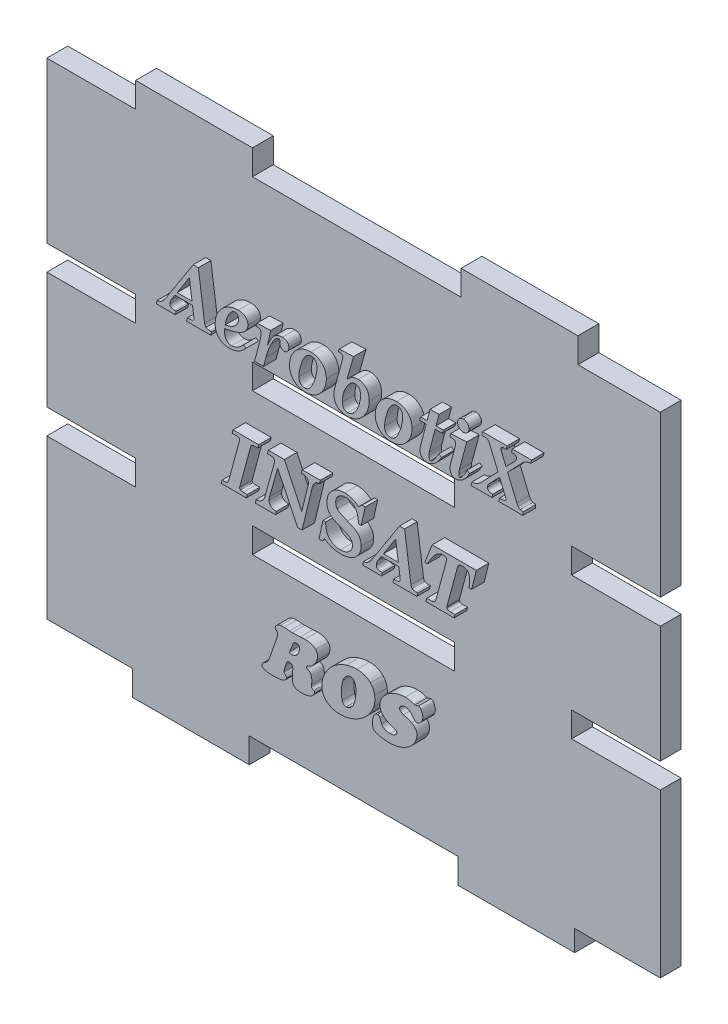
SolidWorks part; units mm, degrees
ref_plane "Front Plane" through (0, 0, 0) normal (0, 0, 1) x (1, 0, 0)
ref_plane "Top Plane" through (0, 0, 0) normal (0, 1, 0) x (1, 0, 0)
ref_plane "Right Plane" through (0, 0, 0) normal (1, 0, 0) x (0, 0, -1)
sketch "Sketch1" plane through (0, 0, 0) normal (0, 0, 1) x (1, 0, 0)
  line L5 (-24, -72.5496) -> (-73.5, -72.5496)
  line L6 (-73.5, 72.5496) -> (73.5, 72.5496)
  line L9 (-73.5, 72.5496) -> (-73.5, -72.5496)
  line L24 (73.5, 72.5496) -> (73.5, -72.5496)
  line L25 (-73.5, 72.5496) -> (73.5, -72.5496) construction
  line L26 (-73.5, -72.5496) -> (73.5, 72.5496) construction
  line L28 (-24, -72.5496) -> (-24, -67.5496)
  line L29 (-24, -67.5496) -> (24, -67.5496)
  line L30 (24, -72.5496) -> (24, -67.5496)
  line L31 (24, -72.5496) -> (73.5, -72.5496)
  line L32 (73.5, 6.4504) -> (73.5, 10.4504) construction
  line L33 (23.9998, -72.5496) -> (-22.4678, -72.5496) construction
  point P0 (0, 0)
  point P5 (0, -67.5496)
  point P12 (24, -67.4165)
  dimension "D1" = 5
  dimension "D2" = 48
extrude "Boss-Extrude1" add sketch "Sketch1" along normal blind 5
sketch "Sketch2" plane through (0, 0, 5) normal (0, 0, 1) x (1, 0, 0)
  line L0 (73.5, -72.5496) -> (73.5, 72.5496) construction
  line L1 (-23.2338, -23.5496) -> (23.2338, -23.5496)
  line L2 (-23.2338, -23.5496) -> (-23.2338, -27.5496)
  line L3 (-23.2338, -27.5496) -> (23.2338, -27.5496)
  line L4 (23.2338, -23.5496) -> (23.2338, -27.5496)
  line L5 (53.2338, -23.5496) -> (73.5, -23.5496)
  line L6 (53.2338, -23.5496) -> (53.2338, -27.3)
  line L7 (53.2338, -27.3) -> (73.5, -27.3)
  line L8 (73.5, -23.5496) -> (73.5, -27.3)
  line L9 (-73.5, -23.5496) -> (-53.2338, -23.5496)
  line L10 (-73.5, -23.5496) -> (-73.5, -27.5496)
  line L11 (-73.5, -27.5496) -> (-53.2338, -27.5496)
  line L12 (-53.2338, -23.5496) -> (-53.2338, -27.5496)
  line L13 (-75, -67.5627) -> (-53.9636, -67.5627)
  line L14 (-75, -67.5627) -> (-75, -72.5496)
  line L15 (-75, -72.5496) -> (-53.9636, -72.5496)
  line L16 (-53.9636, -67.5627) -> (-53.9636, -72.5496)
  line L17 (53.9998, -68.5496) -> (73.5, -68.5496)
  line L18 (53.9998, -68.5496) -> (53.9998, -72.5496)
  line L19 (53.9998, -72.5496) -> (73.5, -72.5496)
  line L20 (73.5, -68.5496) -> (73.5, -72.5496)
  line L21 (-73.5, -72.5496) -> (-24, -72.5496) construction
extrude "Cut-Extrude1" cut sketch "Sketch2" against normal blind 5
sketch "Sketch4" plane through (0, 0, 5) normal (0, 0, 1) x (1, 0, 0)
  line L9 (-73.5, 72.5496) -> (-73.5, -23.5496) construction
  line L20 (24.766, 54.8659) -> (-23.234, 54.8659) construction
  line L21 (-73.5, 55.8659) -> (-52.234, 55.8659)
  line L22 (-73.5, 55.8659) -> (-73.5, 49.8659)
  line L23 (-73.5, 49.8659) -> (-52.234, 49.8659)
  line L24 (-52.234, 55.8659) -> (-52.234, 49.8659)
  line L25 (-24.234, 55.8659) -> (25.766, 55.8659)
  line L26 (-24.234, 55.8659) -> (-24.234, 49.8659)
  line L27 (-24.234, 49.8659) -> (25.766, 49.8659)
  line L28 (25.766, 55.8659) -> (25.766, 49.8659)
  line L29 (-23.234, 54.8659) -> (-23.234, 50.8659) construction
  line L30 (24.766, 50.8659) -> (24.766, 54.8659) construction
  line L31 (73.5, -23.5496) -> (73.5, 72.5496) construction
  line L32 (53.766, 55.8659) -> (73.5, 55.8659)
  line L33 (53.766, 55.8659) -> (53.766, 49.8659)
  line L34 (53.766, 49.8659) -> (73.5, 49.8659)
  line L35 (73.5, 55.8659) -> (73.5, 49.8659)
  line L36 (74.4144, 54.8659) -> (54.766, 54.8659) construction
  line L37 (54.766, 54.8659) -> (54.766, 50.8659) construction
  line L38 (74.4144, 50.8659) -> (54.766, 50.8659) construction
  line L39 (-53.234, 54.8659) -> (-72.8824, 54.8659) construction
  line L40 (-53.234, 50.8659) -> (-72.8824, 50.8659) construction
  line L41 (-53.234, 50.8659) -> (-53.234, 54.8659) construction
  dimension "D1" = 1
  dimension "D2" = 1
  dimension "D3" = 6
  dimension "D4" = 1
  dimension "D5" = 1
  dimension "D6" = 1
  dimension "D7" = 1
  dimension "D8" = 1
  dimension "D9" = 1
  dimension "D10" = 1
extrude "Cut-Extrude2" cut sketch "Sketch4" against normal blind 5
sketch "Sketch5" plane through (0, 0, 5) normal (0, 0, 1) x (1, 0, 0)
  line L0 (-73.5, 14.9882) -> (73.5, 14.9882) construction
  line L1 (-73.5, 49.8659) -> (-73.5, -23.5496) construction
  line L2 (73.5, -23.5496) -> (73.5, 49.8659) construction
  text T0 "      AerobotiX" font "Century Schoolbook" height in points 48
extrude "Boss-Extrude2" add sketch "Sketch5" along normal blind 3
sketch "Sketch6" plane through (0, 0, 5) normal (0, 0, 1) x (1, 0, 0)
  line L0 (-73.5, -14.5115) -> (73.5, -14.5115) construction
  line L1 (-73.5, 49.8659) -> (-73.5, -23.5496) construction
  line L2 (73.5, -23.5496) -> (73.5, 49.8659) construction
  text T0 "         INSAT" font "Century Schoolbook" height in points 48
extrude "Boss-Extrude3" add sketch "Sketch6" along normal blind 3
sketch "Sketch7" plane through (0, 0, 5) normal (0, 0, 1) x (1, 0, 0)
  line L0 (-73.5, 49.8659) -> (-73.5, -23.5496) construction
  line L1 (-73.5, 11.4504) -> (-52.2338, 11.4504)
  line L2 (-73.5, 11.4504) -> (-73.5, 5.4504)
  line L3 (-73.5, 5.4504) -> (-52.2338, 5.4504)
  line L4 (-52.2338, 11.4504) -> (-52.2338, 5.4504)
  line L5 (-73.5, 10.4504) -> (73.5, 10.4504) construction
  line L6 (-53.2338, 6.4504) -> (-53.2338, 10.4504) construction
  line L7 (-73.5, 6.4504) -> (73.5, 6.4504) construction
  line L8 (-73.5, 10.4504) -> (73.5, 10.4504) construction
  line L9 (-24.2338, 11.4504) -> (24.2338, 11.4504)
  line L10 (-24.2338, 11.4504) -> (-24.2338, 5.4504)
  line L11 (-24.2338, 5.4504) -> (24.2338, 5.4504)
  line L12 (24.2338, 11.4504) -> (24.2338, 5.4504)
  line L13 (23.2338, 6.4504) -> (23.2338, 10.4504) construction
  line L14 (-73.5, 6.4504) -> (73.5, 6.4504) construction
  line L15 (-23.2338, 6.4504) -> (-23.2338, 10.4504) construction
  line L16 (73.5, -23.5496) -> (73.5, 49.8659) construction
  line L17 (73.5, 11.4504) -> (52.2338, 11.4504)
  line L18 (73.5, 11.4504) -> (73.5, 5.4504)
  line L19 (73.5, 5.4504) -> (52.2338, 5.4504)
  line L20 (52.2338, 11.4504) -> (52.2338, 5.4504)
  line L21 (-73.5, 10.4504) -> (73.5, 10.4504) construction
  line L22 (53.2338, 6.4504) -> (53.2338, 10.4504) construction
  line L23 (-73.5, 6.4504) -> (73.5, 6.4504) construction
  dimension "D1" = 1
  dimension "D2" = 1
  dimension "D3" = 1
  dimension "D4" = 1
  dimension "D5" = 1
  dimension "D6" = 1
  dimension "D7" = 1
  dimension "D8" = 1
  dimension "D9" = 1
  dimension "D10" = 1
extrude "Cut-Extrude3" cut sketch "Sketch7" against normal blind 5
sketch "Sketch8" plane through (0, 0, 5) normal (0, 0, 1) x (1, 0, 0)
  line L1 (-73.5, 55.8659) -> (73.5, 55.8659)
  line L2 (-73.5, 55.8659) -> (-73.5, 72.5496)
  line L3 (-73.5, 72.5496) -> (73.5, 72.5496)
  line L4 (73.5, 55.8659) -> (73.5, 72.5496)
extrude "Cut-Extrude4" cut sketch "Sketch8" against normal through all
sketch "Sketch9" plane through (0, 0, 5) normal (0, 0, 1) x (1, 0, 0)
  line L0 (73.5, -68.5496) -> (73.5, -27.3) construction
  line L1 (-24.2338, -22.5496) -> (24.2338, -22.5496)
  line L2 (-24.2338, -22.5496) -> (-24.2338, -28.5496)
  line L3 (-24.2338, -28.5496) -> (24.2338, -28.5496)
  line L4 (24.2338, -22.5496) -> (24.2338, -28.5496)
  line L5 (52.2338, -22.5496) -> (73.5, -22.5496)
  line L6 (52.2338, -22.5496) -> (52.2338, -28.5496)
  line L7 (52.2338, -28.5496) -> (73.5, -28.5496)
  line L8 (73.5, -22.5496) -> (73.5, -28.5496)
  line L9 (-73.5, -27.5496) -> (-73.5, -67.5627) construction
  line L10 (-52.2338, -22.5496) -> (-73.5, -22.5496)
  line L11 (-52.2338, -22.5496) -> (-52.2338, -28.5496)
  line L12 (-52.2338, -28.5496) -> (-73.5, -28.5496)
  line L13 (-73.5, -22.5496) -> (-73.5, -28.5496)
  line L14 (-53.2338, -23.5496) -> (-73.5, -23.5496) construction
  line L15 (-53.2338, -27.5496) -> (-53.2338, -23.5496) construction
  line L16 (-73.5, -27.5496) -> (-53.2338, -27.5496) construction
  line L17 (23.2338, -23.5496) -> (-23.2338, -23.5496) construction
  line L18 (-23.2338, -23.5496) -> (-23.2338, -27.5496) construction
  line L19 (-23.2338, -27.5496) -> (23.2338, -27.5496) construction
  line L20 (23.2338, -27.5496) -> (23.2338, -23.5496) construction
  line L21 (73.5, -23.5496) -> (53.2338, -23.5496) construction
  line L22 (53.2338, -23.5496) -> (53.2338, -27.3) construction
  line L23 (-73.5, -27.5496) -> (73.5, -27.5496) construction
  line L30 (52.9998, -72.5496) -> (73.5, -72.5496)
  line L31 (73.5, -72.5496) -> (73.5, -67.5496)
  line L32 (52.9998, -67.5496) -> (52.9998, -72.5496)
  line L33 (73.5, -67.5496) -> (52.9998, -67.5496)
  line L34 (52.9998, -67.5496) -> (52.9998, -72.5496)
  line L35 (73.5, -67.5496) -> (52.9998, -67.5496)
  line L43 (-25, -72.5496) -> (25, -72.5496)
  line L46 (-25, -72.5496) -> (-25, -66.5496)
  line L47 (-25, -66.5496) -> (25, -66.5496)
  line L48 (25, -66.5496) -> (25, -72.5496)
  line L49 (-25, -72.5496) -> (-25, -66.5496)
  line L50 (-25, -66.5496) -> (25, -66.5496)
  line L51 (25, -66.5496) -> (25, -72.5496)
  line L53 (-52.9636, -72.5496) -> (-73.5, -72.5496)
  line L54 (-73.5, -72.5496) -> (-73.5, -66.5627)
  line L55 (-52.9636, -72.5496) -> (-52.9636, -66.5627)
  line L56 (-52.9636, -66.5627) -> (-73.5, -66.5627)
  line L57 (-52.9636, -72.5496) -> (-52.9636, -66.5627)
  line L58 (-52.9636, -66.5627) -> (-73.5, -66.5627)
  dimension "D1" = 1
  dimension "D2" = 1
  dimension "D3" = 1
  dimension "D4" = 1
  dimension "D5" = 1
  dimension "D6" = 1
  dimension "D7" = 1
  dimension "D8" = 1
  dimension "D9" = 1
  dimension "D10" = 1
  dimension "D12" = 1
  dimension "D14" = 1
  dimension "D15" = 1
extrude "Cut-Extrude5" cut sketch "Sketch9" against normal through all
sketch "Sketch10" plane through (0, 0, 5) normal (0, 0, 1) x (1, 0, 0)
  line L0 (-73.5, -48.0496) -> (73.5, -48.0496) construction
  line L1 (-73.5, -28.5496) -> (-73.5, -66.5627) construction
  line L2 (73.5, -67.5496) -> (73.5, -28.5496) construction
  text T0 "             ROS" font "Cooper Black" height in points 48
extrude "Boss-Extrude4" add sketch "Sketch10" along normal blind 3
